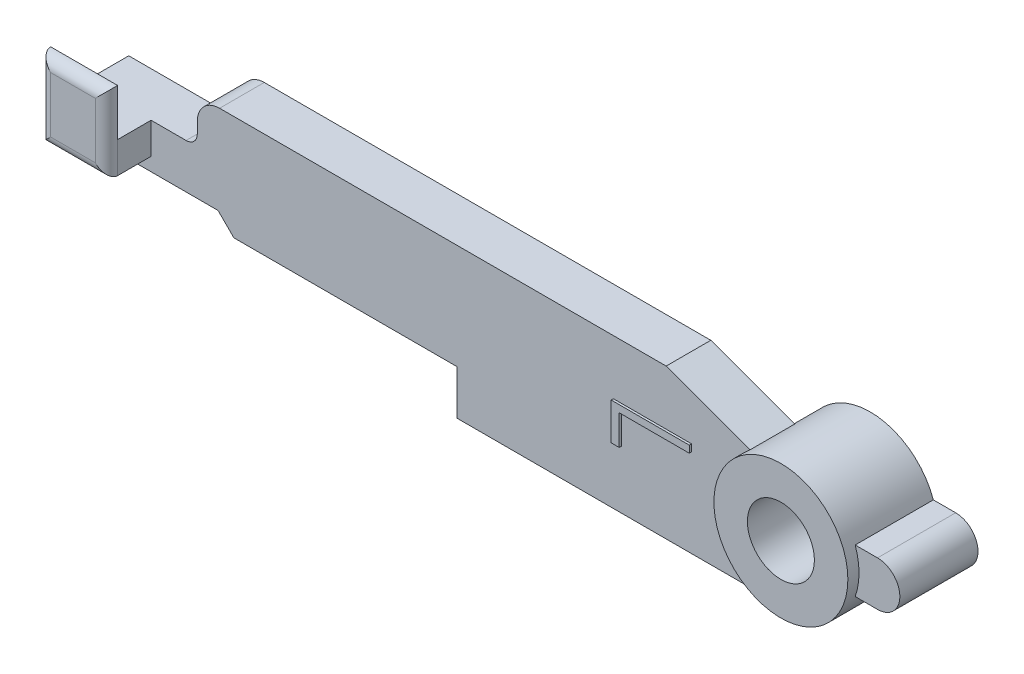
SolidWorks part; units mm, degrees
ref_plane "Piano frontale" through (0, 0, 0) normal (0, 0, 1) x (1, 0, 0)
ref_plane "Piano superiore" through (0, 0, 0) normal (0, 1, 0) x (1, 0, 0)
ref_plane "Piano destro" through (0, 0, 0) normal (1, 0, 0) x (0, 0, -1)
sketch "Schizzo1" plane through (0, 0, 0) normal (0, 0, 1) x (1, 0, 0)
  line L0 (19.0188, 0) -> (-19.0188, 0) construction
  line L1 (0, 0) -> (0, 8.6004) construction
  line L2 (-16.7071, 0.7929) -> (-10.7071, 0.7929)
  line L3 (-10.7071, 0.7929) -> (-10, 1.5)
  line L4 (-10, 1.5) -> (0, 1.5)
  line L5 (0, 1.5) -> (0, 3.5)
  line L6 (0, 3.5) -> (15, 3.5)
  line L7 (15, 3.5) -> (15, 0)
  line L8 (15, 0) -> (15, -1.155)
  line L9 (15, -1.155) -> (9.3618, -3.2071)
  line L10 (9.3618, -3.2071) -> (-11.6382, -3.2071)
  line L11 (-11.6382, -3.2071) -> (-11.6382, -1.2071)
  line L12 (-11.6382, -1.2071) -> (-16.7071, -1.2071)
  line L13 (-16.7071, -1.2071) -> (-16.7071, 0.7929)
  point P4 (0, 0)
  dimension "D1" = 15
  dimension "D2" = 10
  dimension "D3" = 6
  dimension "D4" = 1
  dimension "D5" = 2
  dimension "D6" = 6
  dimension "D7" = 20
  dimension "D8" = 21
  dimension "D9" = 3.5
  dimension "D10" = 45
  dimension "D11" = 2
  dimension "D12" = 2
extrude "Estrusione-Estrusione1" add sketch "Schizzo1" along normal blind 2
fillet "Raccordo1" radius 1 1 edges at (-11.6382, -3.2071, 1)
fillet "Raccordo2" radius 0.5 1 edges at (-11.6382, -1.2071, 1)
sketch "Schizzo2" plane through (0, 0, 0) normal (0, 0, 1) x (1, 0, 0)
  line L0 (-10.7071, 0.7929) -> (22.9117, 0.7929) construction
  line L1 (15, -1.155) -> (15, 3.5) construction
  line L2 (15, 3.5) -> (0, 3.5) construction
  circle A0 centre (15, 0.5) radius 3
  dimension "D1" = 6
extrude "Estrusione-Estrusione2" add sketch "Schizzo2" along direction (0, 0, -1) on the side of the normal blind 2.5 and the other way blind 1.5
sketch "Schizzo3" plane through (0, 0, 0) normal (0, 0, 1) x (1, 0, 0)
  line L0 (15, 0.5) -> (16.6892, 0.5) construction
  line L1 (18.8284, 1.5) -> (17.8284, 1.5)
  line L4 (18.8284, -0.5) -> (17.8284, -0.5)
  line L5 (18.8284, 1.5) -> (18.8284, 0.5) construction
  arc A1 (18.8284, -0.5) -> (18.8284, 1.5) centre (18.8284, 0.5) ccw
  circle A2 centre (15, 0.5) radius 3 construction
  arc A3 (17.8284, -0.5) -> (17.8284, 1.5) centre (15, 0.5) ccw
  dimension "D2" = 1
  dimension "D3" = 1
  dimension "D4" = 1
extrude "Estrusione-Estrusione3" add sketch "Schizzo3" along normal up to surface and the other way up to surface up to face at (-4.9758, -0.1872, 2) other way up to face at (18, 0.5, -1.5)
sketch "Schizzo4" plane through (-16.7071, 0, 0) normal (-1, 0, 0) x (0, 0, 1)
  line L0 (2, -1.2071) -> (3.5, -1.2071)
  line L1 (3.5, -1.2071) -> (3.5, -3.3071)
  line L2 (3.5, -3.3071) -> (4, -3.3071)
  line L3 (4, -3.3071) -> (4, 0.1929)
  line L4 (4, 0.1929) -> (2, 0.1929)
  line L5 (2, 0.7929) -> (2, -1.2071) construction
  line L6 (2, 0.1929) -> (2, -1.2071)
  line L9 (0, 0.7929) -> (0, -1.2071) construction
  dimension "D1" = 1.4
  dimension "D2" = 3.5
  dimension "D3" = 0.5
  dimension "D4" = 4
extrude "Estrusione-Estrusione4" add sketch "Schizzo4" against normal blind 3
fillet "Raccordo3" radius 0.5 4 edges at (-15.2071, 0.1929, 4) (-13.7071, -1.5571, 4) (-15.2071, -3.3071, 4) (-16.7071, -1.5571, 4)
sketch "Schizzo5" plane through (0, 0, 2.5) normal (0, 0, 1) x (1, 0, 0)
  circle A0 centre (15, 0.5) radius 1.5
  circle A1 centre (15, 0.5) radius 3 construction
  dimension "D1" = 1.5
extrude "Taglio-Estrusione1" cut sketch "Schizzo5" against normal through all
mirror "Specchia2" about plane through (0, 0, 0) normal (0, 1, 0) of bodies 105 106
delete or keep bodies "Corpo-Elimina/Mantieni 1" type delete bodies bodies 105
sketch "Schizzo6" plane through (0, 0, 2) normal (0, 0, 1) x (1, 0, 0)
  line L0 (7, 1.2071) -> (7, -3.5) construction
  line L1 (15, -3.5) -> (0, -3.5) construction
  line L2 (0, -3.5) -> (0, -1.5) construction
  line L5 (-10.6382, 3.2071) -> (9.3618, 3.2071) construction
  text T0 "L\r\n"
  dimension "D1" = 7
  dimension "D2" = 2
extrude "Estrusione-Estrusione5" add sketch "Schizzo6" along normal blind 0.1
sketch "Schizzo8" plane through (0, 0, 0) normal (0, 0, -1) x (-1, 0, 0)
  line L1 (16.7071, 1.2071) -> (13.7071, 1.2071) construction
  line L2 (16.7071, 1.2071) -> (16.7071, -0.1929) construction
  line L3 (16.7071, -0.1929) -> (13.7071, -0.1929) construction
  line L4 (13.7071, 1.2071) -> (13.7071, -0.1929) construction
  line L5 (16.7071, 1.2071) -> (13.7071, -0.1929) construction
  line L6 (16.7071, -0.1929) -> (13.7071, 1.2071) construction
  line L7 (13.7071, -0.1929) -> (16.7071, -0.1929) construction
  line L8 (13.7071, -0.1929) -> (16.7071, -0.1929)
  point P4 (15.2071, 0.5071)
ref_axis "Assi1" through (-15.2071, 0.5071, 5.921) along (0, 0, -1)
